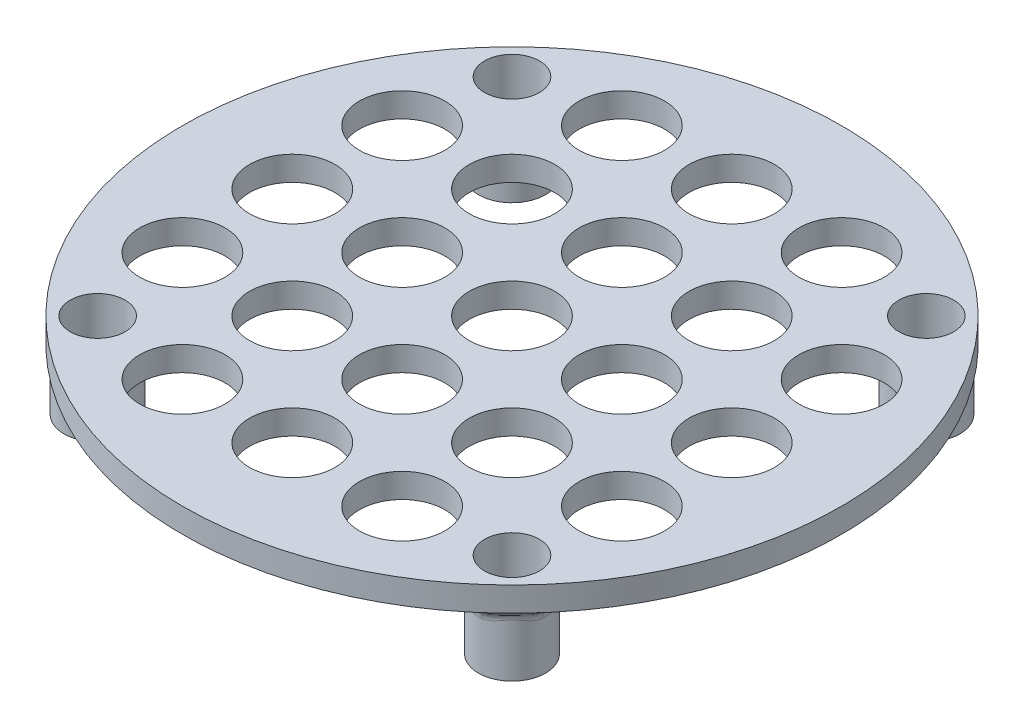
SolidWorks part; units mm, degrees
ref_plane "前视基准面" through (0, 0, 0) normal (0, 0, 1) x (1, 0, 0)
ref_plane "上视基准面" through (0, 0, 0) normal (0, 1, 0) x (1, 0, 0)
ref_plane "右视基准面" through (0, 0, 0) normal (1, 0, 0) x (0, 0, -1)
sketch "草图1" plane through (0, 0, 0) normal (0, 1, 0) x (1, 0, 0)
  line L0 (0, 0) -> (27, 0) construction
  line L1 (0, 0) -> (0, 27) construction
  line L2 (0, 0) -> (19.0919, 19.0919) construction
  line L3 (0, 0) -> (-19.0919, -19.0919) construction
  line L4 (0, 0) -> (13.2351, -13.2351) construction
  circle A1 centre (0, 0) radius 27
  circle A2 centre (16.9706, 16.9706) radius 2.75
  circle A4 centre (16.9706, -16.9706) radius 2.75
  circle A5 centre (-16.9706, -16.9706) radius 2.75
  circle A6 centre (-16.9706, 16.9706) radius 2.75
  point P16 (5, 0)
  dimension "D1" = 4
  dimension "D2" = 54
  dimension "D4" = 5.5
  dimension "D3" = 24
extrude "凸台-拉伸1" add sketch "草图1" along normal blind 2 contours A1 A2 | A6 | A5 | A4 | A2 region at (0, 0, 0) region at (16.9706, 0, -16.9706) region at (16.9706, 0, 16.9706) region at (-16.9706, 0, 16.9706) region at (-16.9706, 0, -16.9706)
extrude "凸台-拉伸2" add sketch "草图1<3>" against normal blind 5 contours A6 | A5 | A4 | A2 region at (16.9706, 0, -16.9706) region at (16.9706, 0, 16.9706) region at (-16.9706, 0, 16.9706) region at (-16.9706, 0, -16.9706)
sketch "草图1<3>" plane through (0, 0, 0) normal (0, 1, 0) x (1, 0, 0) same geometry as "草图1"
sketch "草图2" plane through (0, 2, 0) normal (0, 1, 0) x (1, 0, 0)
  circle A0 centre (-16.9706, -16.9706) radius 2.25
  circle A1 centre (16.9706, -16.9706) radius 2.75
  circle A2 centre (16.9706, -16.9706) radius 2.75
  circle A3 centre (16.9706, 16.9706) radius 2.75
  circle A4 centre (16.9706, 16.9706) radius 2.75
  circle A5 centre (0, 0) radius 27
  circle A6 centre (0, 0) radius 27
  circle A7 centre (-16.9706, 16.9706) radius 2.75
  circle A8 centre (-16.9706, 16.9706) radius 2.75
  circle A9 centre (-16.9706, -16.9706) radius 2.75
  circle A10 centre (-16.9706, -16.9706) radius 2.75
  circle A11 centre (-16.9706, -16.9706) radius 1.3
  circle A12 centre (-16.9706, 16.9706) radius 2.25
  circle A13 centre (-16.9706, 16.9706) radius 1.3
  circle A14 centre (16.9706, 16.9706) radius 2.25
  circle A15 centre (16.9706, 16.9706) radius 1.3
  circle A16 centre (16.9706, -16.9706) radius 2.25
  circle A17 centre (16.9706, -16.9706) radius 1.3
  dimension "D6" = 4.5
  dimension "D7" = 2.6
  dimension "D1" = 0
  dimension "D2" = 0
  dimension "D3" = 0
  dimension "D4" = 0
  dimension "D5" = 0
  dimension "D8" = 4
extrude "切除-拉伸1" cut sketch "草图2" against normal blind 5 contours A0 A11 | A11 | A12 A13 | A13 | A14 A15 | A15 | A16 A17 | A17 region at (-19.1569, 2, 16.9706) region at (-16.9706, 2, 16.9706) region at (-19.1569, 2, -16.9706) region at (-16.9706, 2, -16.9706) region at (14.7842, 2, -16.9706) region at (16.9706, 2, -16.9706) region at (14.7842, 2, 16.9706) region at (16.9706, 2, 16.9706)
extrude "切除-拉伸2" cut sketch "草图2<4>" against normal blind 7 contours A17 | A11 | A13 | A15 region at (-16.9706, 2, 16.9706) region at (-16.9706, 2, -16.9706) region at (16.9706, 2, -16.9706) region at (16.9706, 2, 16.9706)
sketch "草图2<4>" plane through (0, 2, 0) normal (0, 1, 0) x (1, 0, 0) same geometry as "草图2"
sketch "草图3" plane through (0, 2, 0) normal (0, 1, 0) x (1, 0, 0)
  circle A0 centre (0, 0) radius 3.5
  circle A1 centre (9, 0) radius 3.5
  circle A2 centre (18, 0) radius 3.5
  circle A3 centre (9, 9) radius 3.5
  circle A4 centre (18, 9) radius 3.5
  circle A5 centre (9, 18) radius 3.5
  circle A6 centre (18, 18) radius 3.5
  circle A7 centre (0, 9) radius 3.5
  circle A8 centre (0, 18) radius 3.5
  circle A9 centre (9, 0) radius 3.5
  circle A10 centre (18, 0) radius 3.5
  circle A11 centre (18, -9) radius 3.5
  circle A12 centre (9, -9) radius 3.5
  circle A13 centre (0, -9) radius 3.5
  circle A14 centre (0, -18) radius 3.5
  circle A15 centre (9, -18) radius 3.5
  circle A16 centre (0, -9) radius 3.5
  circle A17 centre (0, -18) radius 3.5
  circle A18 centre (-9, -18) radius 3.5
  circle A19 centre (-9, -9) radius 3.5
  circle A20 centre (-9, 0) radius 3.5
  circle A21 centre (-18, 0) radius 3.5
  circle A22 centre (-18, -9) radius 3.5
  circle A23 centre (-9, 0) radius 3.5
  circle A24 centre (-18, 0) radius 3.5
  circle A25 centre (-18, 9) radius 3.5
  circle A26 centre (-9, 9) radius 3.5
  circle A27 centre (0, 9) radius 3.5
  circle A28 centre (0, 18) radius 3.5
  circle A29 centre (-9, 18) radius 3.5
  dimension "D3" = 7
  dimension "D1" = 3
  dimension "D2" = 3
  dimension "D4" = 4
extrude "切除-拉伸3" cut sketch "草图3" against normal blind 6 contours A11 | A2 | A4 | A5 | A3 | A1 | A12 | A15 | A14 | A13 | A0 | A7 | A8 | A29 | A26 | A20 | A19 | A18 | A22 | A21 | A25 region at (0, 2, 0) region at (9, 2, 0) region at (18, 2, 0) region at (9, 2, -9) region at (18, 2, -9) region at (9, 2, -18) region at (0, 2, -9) region at (0, 2, -18) region at (18, 2, 9) region at (9, 2, 9) region at (0, 2, 9) region at (0, 2, 18) region at (9, 2, 18) region at (-9, 2, 18) region at (-9, 2, 9) region at (-9, 2, 0) region at (-18, 2, 0) region at (-18, 2, 9) region at (-18, 2, -9) region at (-9, 2, -9) region at (-9, 2, -18)
fillet "圆角1" radius 1 4 edges at (16.9706, 0, 19.7206) (-16.9706, 0, 19.7206) (-16.9706, 0, -14.2206) (16.9706, 0, -14.2206)
